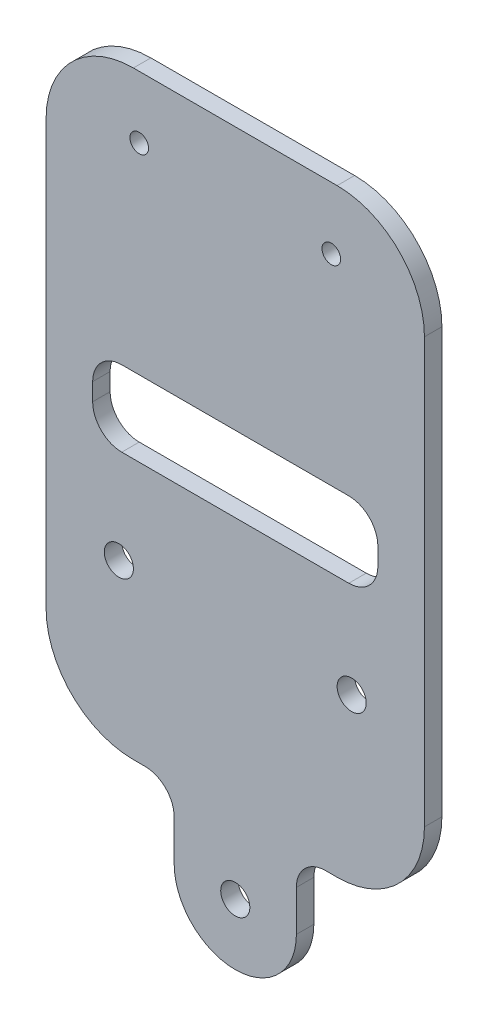
SolidWorks part; units mm, degrees
material "2024 Alloy"
ref_plane "Front Plane" through (0, 0, 0) normal (0, 0, 1) x (1, 0, 0)
ref_plane "Top Plane" through (0, 0, 0) normal (0, 1, 0) x (1, 0, 0)
ref_plane "Right Plane" through (0, 0, 0) normal (1, 0, 0) x (0, 0, -1)
sketch "Sketch2" plane through (0, 0, 0) normal (0, 0, 1) x (1, 0, 0)
  line L1 (-100, 100) -> (100, 100)
  line L2 (-100, 100) -> (-100, -100)
  line L3 (-100, -100) -> (100, -100)
  line L4 (100, 100) -> (100, -100)
  line L5 (-100, 100) -> (100, -100) construction
  line L6 (-100, -100) -> (100, 100) construction
  point P0 (0, 0)
  dimension "D1" = 200
extrude "Boss-Extrude1" add sketch "Sketch2" along normal blind 3
sketch "Sketch3" plane through (0, 0, 0) normal (0, 0, -1) x (-1, 0, 0)
  line L1 (-44.5, 23.75) -> (44.5, 23.75) construction
  line L2 (-44.5, 23.75) -> (-44.5, -23.75) construction
  line L3 (-44.5, -23.75) -> (44.5, -23.75) construction
  line L4 (44.5, 23.75) -> (44.5, -23.75) construction
  line L5 (-44.5, 23.75) -> (44.5, -23.75) construction
  line L6 (-44.5, -23.75) -> (44.5, 23.75) construction
  circle A0 centre (-32.4, 11.65) radius 2.5
  circle A1 centre (7.6, 11.65) radius 2.5
  circle A2 centre (-12.4, -28.75) radius 2.5
  point P0 (0, 0)
  dimension "D7" = 5
  dimension "D1" = 89
  dimension "D2" = 47.5
  dimension "D3" = 12.1
  dimension "D4" = 12.1
  dimension "D5" = 12.1
  dimension "D6" = 40
  dimension "D8" = 20
  dimension "D9" = 5
extrude "Cut-Extrude1" cut sketch "Sketch3" against normal blind 10
sketch "Sketch4" plane through (0, 0, 3) normal (0, 0, 1) x (1, 0, 0)
  line L1 (-20.1, 86.1635) -> (44.9, 86.1635)
  line L7 (-20.1, 28.331) -> (-20.1, 86.1635)
  line L8 (44.9, 28.331) -> (44.9, -16.75)
  line L10 (22.9, -28.75) -> (22.9, -16.75)
  line L11 (1.9, -34.4037) -> (1.9, -16.75)
  line L12 (1.9, -16.75) -> (-20.1, -16.75)
  line L13 (-20.1, -16.75) -> (-20.1, 28.331)
  line L14 (22.9, -16.75) -> (44.9, -16.75)
  line L15 (44.9, 28.331) -> (44.9, 86.1635)
  line L16 (25.9, 60.853) -> (25.9, 34.5762) construction
  line L17 (25.9, 55.5) -> (25.9, 73.5) construction
  line L18 (-1.9, 60.853) -> (-1.9, 34.5762) construction
  line L19 (-1.9, 55.5) -> (-1.9, 73.5) construction
  line L20 (12, 59.8279) -> (12, 40.2509) construction
  line L22 (0.825, 49.5) -> (23.175, 49.5) construction
  line L23 (0.825, 49.5) -> (0.825, 26.5) construction
  line L24 (0.825, 26.5) -> (23.175, 26.5) construction
  line L25 (23.175, 49.5) -> (23.175, 26.5) construction
  line L26 (0.825, 49.5) -> (23.175, 26.5) construction
  line L27 (0.825, 26.5) -> (23.175, 49.5) construction
  line L28 (30.15, 49.5) -> (-6.15, 49.5) construction
  line L30 (-12.1, 41) -> (36.9, 41)
  line L31 (-12.1, 41) -> (-12.1, 28)
  line L32 (-12.1, 28) -> (36.9, 28)
  line L33 (36.9, 41) -> (36.9, 28)
  line L34 (-12.1, 41) -> (36.9, 28) construction
  line L35 (-12.1, 28) -> (36.9, 41) construction
  circle A2 centre (12.4, -28.75) radius 10.5
  point P0 (12.4, 34.5)
  point P20 (12.4, 86.1635)
  point P36 (12, 38)
  line M6 (100, -100) -> (100, 100)
  line M7 (100, 100) -> (-100, 100)
  line M8 (-100, 100) -> (-100, -100)
  line M9 (-100, -100) -> (100, -100)
  dimension "D5" = 21
  dimension "D1" = 8.5
  dimension "D2" = 13
  dimension "D3" = 65
  dimension "D4" = 8
  dimension "D6" = 23
  dimension "D7" = 22.35
  dimension "D8" = 8
extrude "Cut-Extrude2" cut sketch "Sketch4" against normal up to next contours A2 L11 L12 L13 L7 L15 L8 L14 L10 M7 M8 M9 M6 | L33 L30 L31 L32 region at (12.4, 34.5, 3) region at (0, -97.1716, 3)
fillet "Fillet1" radius 15 4 edges at (-20.1, -16.75, 1.5) (44.9, -16.75, 1.5) (-20.1, 86.1635, 1.5) (44.9, 86.1635, 1.5)
fillet "Fillet2" radius 5 6 edges at (-12.1, 41, 1.5) (-12.1, 28, 1.5) (36.9, 41, 1.5) (36.9, 28, 1.5) (1.9, -16.75, 1.5) (22.9, -16.75, 1.5)
sketch "Sketch6" plane through (0, 0, 3) normal (0, 0, 1) x (1, 0, 0)
  line L0 (-20.1, 71.1635) -> (-20.1, -1.75) construction
  line L1 (12.4, 15.6544) -> (12.4, 118.239) construction
  line L12 (31.9, 41) -> (-7.1, 41) construction
  circle A0 centre (-4.1, 75.5) radius 1.6
  circle A1 centre (28.9, 75.5) radius 1.6
  dimension "D1" = 3.2
  dimension "D3" = 34.5
  dimension "D2" = 16
extrude "Cut-Extrude4" cut sketch "Sketch6" against normal up to next contours A1 | A0 region at (-4.1, 75.5, 3) region at (28.9, 75.5, 3)
